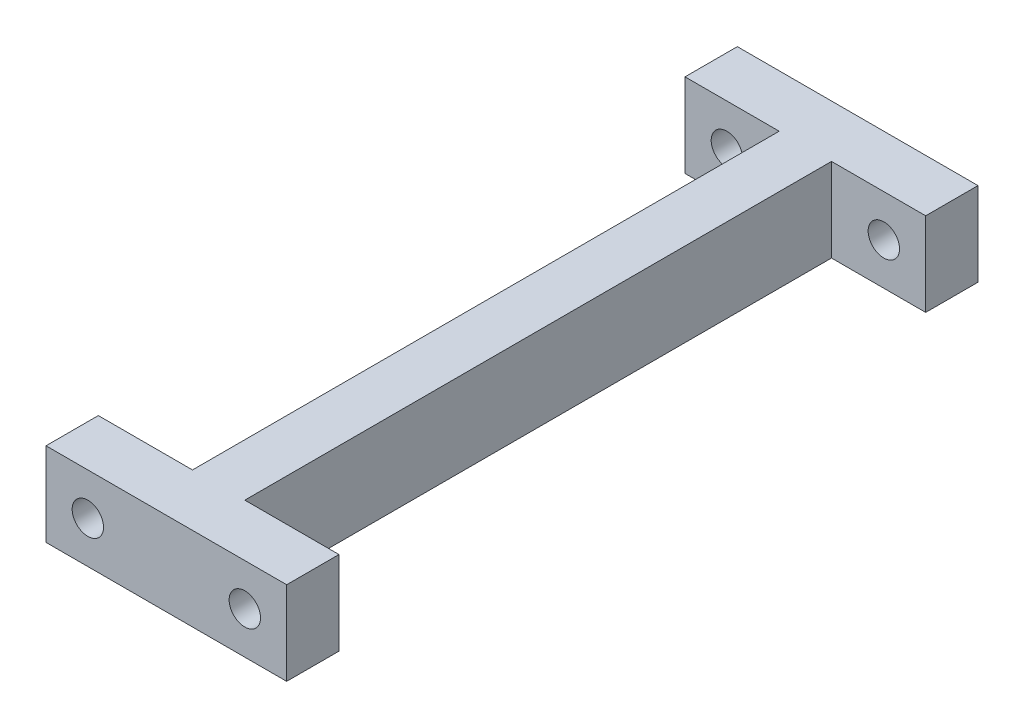
SolidWorks part; units mm, degrees
ref_plane "Front Plane" through (0, 0, 0) normal (0, 0, 1) x (1, 0, 0)
ref_plane "Top Plane" through (0, 0, 0) normal (0, 1, 0) x (1, 0, 0)
ref_plane "Right Plane" through (0, 0, 0) normal (1, 0, 0) x (0, 0, -1)
sketch "Sketch1" plane through (0, 0, 0) normal (0, 0, 1) x (1, 0, 0)
  line L0 (0, 0) -> (4, 4) construction
  line L1 (0, 0) -> (23, 0)
  line L2 (0, 0) -> (0, 8)
  line L3 (0, 8) -> (23, 8)
  line L4 (23, 0) -> (23, 8)
  line L5 (4, 4) -> (19, 4) construction
  line L6 (19, 4) -> (23, 0) construction
  line L7 (0, 8) -> (4, 4) construction
  line L8 (19, 4) -> (23, 8) construction
  circle A0 centre (4, 4) radius 1.5
  circle A1 centre (19, 4) radius 1.5
  point P9 (2.6887, 1.7001)
  dimension "D1" = 3
  dimension "D2" = 8
  dimension "D3" = 23
  dimension "D4" = 15
extrude "Boss-Extrude1" add sketch "Sketch1" along normal blind 5
sketch "Sketch2" plane through (0, 0, 5) normal (0, 0, 1) x (1, 0, 0)
  line L0 (23, 8) -> (0, 8) construction
  line L1 (9, 8) -> (14, 8)
  line L2 (9, 8) -> (9, 0)
  line L3 (9, 0) -> (14, 0)
  line L4 (14, 8) -> (14, 0)
  line L5 (0, 0) -> (23, 0) construction
  line L6 (0, 8) -> (9, 0) construction
  line L7 (23, 8) -> (14, 0) construction
  line L8 (9, 0) -> (14, 8) construction
  line L9 (9, 8) -> (14, 0) construction
  line L10 (11.5, 8) -> (11.5, 0) construction
  dimension "D1" = 5
extrude "Boss-Extrude2" add sketch "Sketch2" along normal blind 61.0706
sketch "Sketch4" plane through (0, 0, 66.0706) normal (0, 0, 1) x (1, 0, 0)
  line L0 (23, 0) -> (23, 8) construction
  line L1 (0, 0) -> (23, 0) construction
  line L2 (0, 0) -> (0, 8) construction
  line L3 (0, 8) -> (23, 8) construction
  line L4 (23, 0) -> (23, 8)
  line L5 (0, 0) -> (23, 0)
  line L6 (0, 0) -> (0, 8)
  line L7 (0, 8) -> (23, 8)
  circle A0 centre (4, 4) radius 1.5 construction
  circle A1 centre (19, 4) radius 1.5 construction
  circle A2 centre (4, 4) radius 1.5
  circle A3 centre (19, 4) radius 1.5
extrude "Boss-Extrude3" add sketch "Sketch4" against normal blind 5
